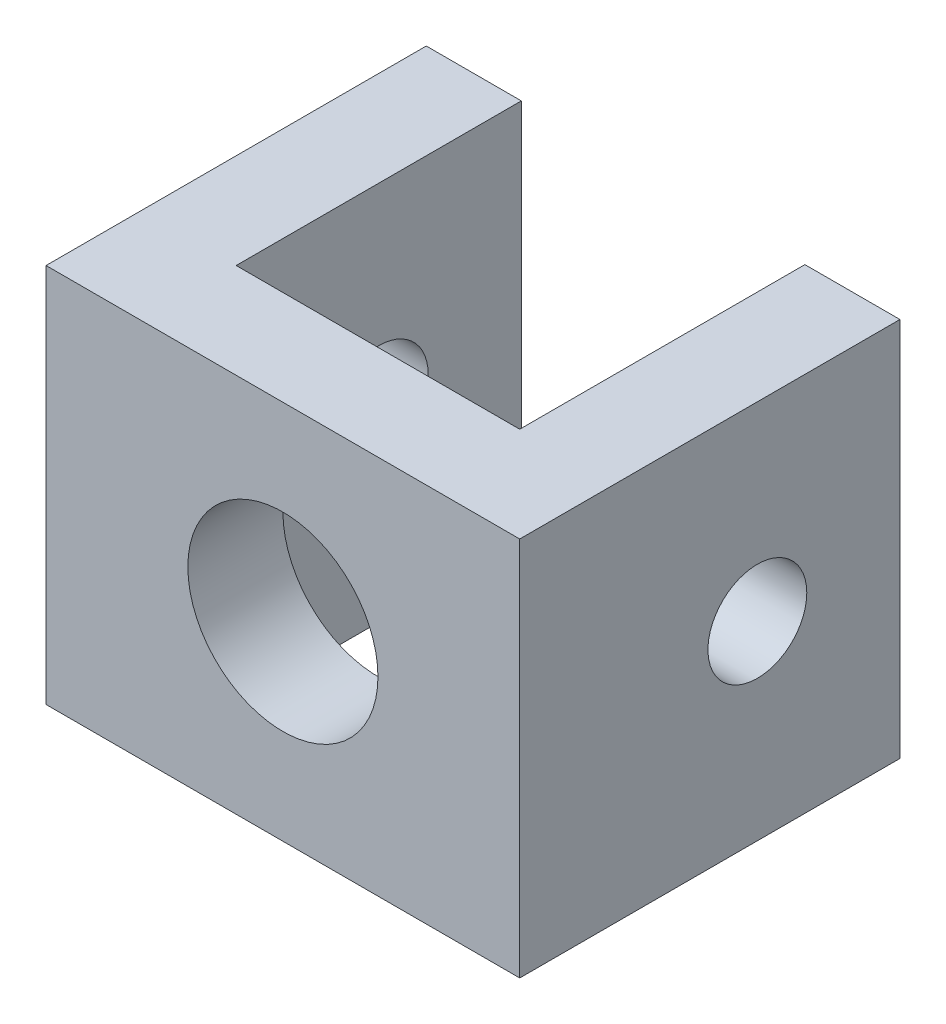
SolidWorks part; units mm, degrees
ref_plane "Front Plane" through (0, 0, 0) normal (0, 0, 1) x (1, 0, 0)
ref_plane "Top Plane" through (0, 0, 0) normal (0, 1, 0) x (1, 0, 0)
ref_plane "Right Plane" through (0, 0, 0) normal (1, 0, 0) x (0, 0, -1)
sketch "Sketch1" plane through (0, 0, 0) normal (0, 1, 0) x (1, 0, 0)
  line L0 (0, 0) -> (0, 25.4)
  line L1 (0, 25.4) -> (6.35, 25.4)
  line L2 (6.35, 25.4) -> (6.35, 6.35)
  line L3 (6.35, 6.35) -> (25.2944, 6.35)
  line L7 (31.6444, 0) -> (0, 0)
  line L8 (15.8222, 0) -> (15.8222, 6.35) construction
  line L9 (31.6444, 25.4) -> (25.2944, 25.4)
  line L10 (25.2944, 25.4) -> (25.2944, 6.35)
  line L11 (31.6444, 0) -> (31.6444, 25.4)
  dimension "D1" = 6.35
  dimension "D2" = 6.35
  dimension "D3" = 25.4
extrude "Boss-Extrude1" add sketch "Sketch1" along normal blind 25.4
sketch "Sketch2" plane through (0, 0, 0) normal (0, 0, 1) x (1, 0, 0)
  line L0 (15.8222, 25.4) -> (15.8222, 0) construction
  line L1 (0, 25.4) -> (31.6444, 25.4) construction
  line L2 (0, 0) -> (31.6444, 0) construction
  line L3 (0, 12.7) -> (31.6444, 12.7) construction
  line L4 (0, 25.4) -> (0, 0) construction
  line L5 (31.6444, 25.4) -> (31.6444, 0) construction
  circle A0 centre (15.8222, 12.7) radius 6.35
  point P14 (15.8222, 12.7)
  point P15 (0, 0)
extrude "Cut-Extrude1" cut sketch "Sketch2" against normal through all
sketch "Sketch5" plane through (6.35, 0, 0) normal (1, 0, 0) x (0, 0, -1)
  line L0 (6.35, 12.7) -> (25.4, 12.7) construction
  line L1 (6.35, 25.4) -> (6.35, 0) construction
  line L2 (25.4, 25.4) -> (25.4, 0) construction
  line L3 (15.875, 25.4) -> (15.875, 0) construction
  line L4 (6.35, 25.4) -> (25.4, 25.4) construction
  line L5 (6.35, 0) -> (25.4, 0) construction
  circle A0 centre (15.875, 12.7) radius 3.302
extrude "Cut-Extrude2" cut sketch "Sketch5" against normal through all and the other way through all
